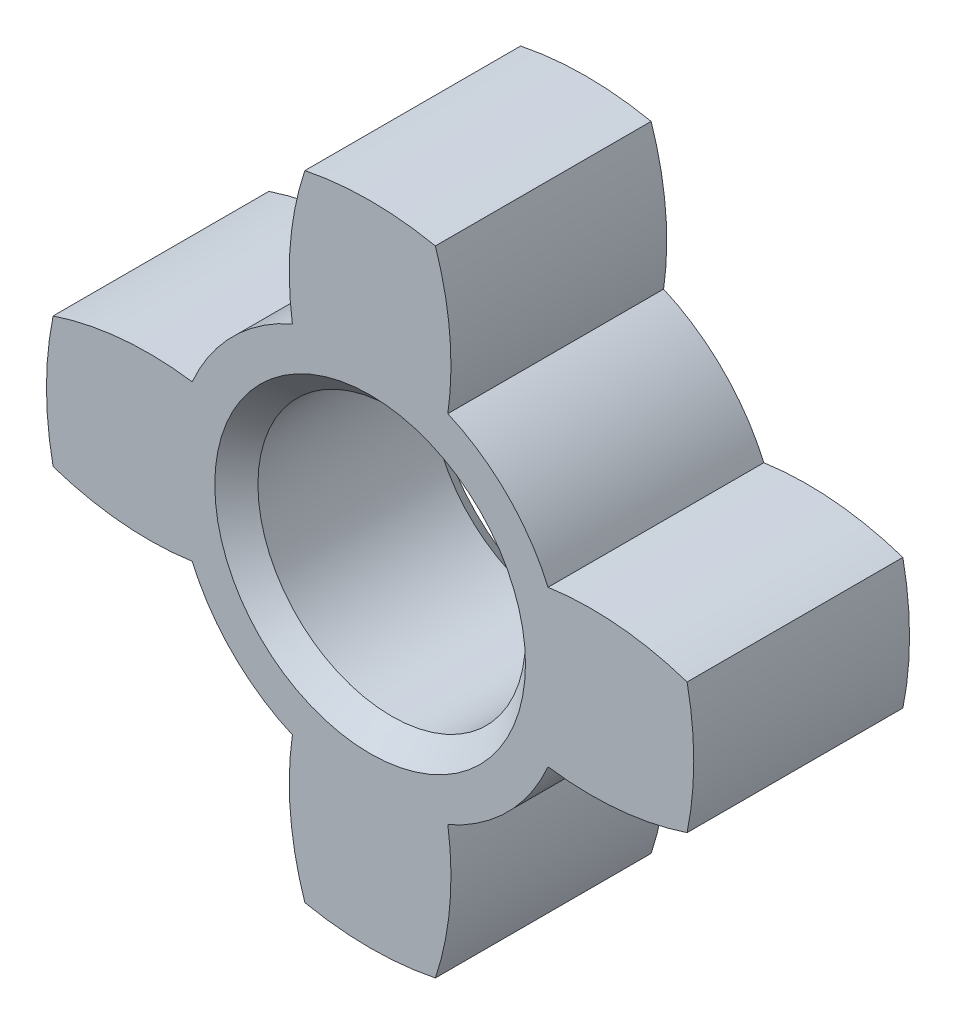
SolidWorks part; units mm, degrees
ref_plane "Front Plane" through (0, 0, 0) normal (0, 0, 1) x (1, 0, 0)
ref_plane "Top Plane" through (0, 0, 0) normal (0, 1, 0) x (1, 0, 0)
ref_plane "Right Plane" through (0, 0, 0) normal (1, 0, 0) x (0, 0, -1)
sketch "Sketch1" plane through (0, 0, 0) normal (1, 0, 0) x (0, 0, -1)
  line L0 (-5, 7.5) -> (-5, 3.6)
  line L1 (-5, 3.6) -> (-4.5, 3.1)
  line L2 (-4.5, 3.1) -> (-0.5, 3.1)
  line L3 (-0.5, 3.1) -> (0, 3.6)
  line L4 (0, 3.6) -> (0, 7.5)
  line L5 (0, 7.5) -> (-5, 7.5)
  line L6 (0, 0) -> (-5, 0) construction
revolve "Revolve1" add sketch "Sketch1" angle 360 about L6 reverse direction yes
sketch "Sketch2" plane through (0, 0, 0) normal (0, 0, 1) x (1, 0, 0)
  circle A0 centre (0, 0) radius 15
  arc A1 (-9.8929, 0) -> (-4.1238, -1.8013) centre (-5.1265, 5.1265) ccw
  arc A2 (-4.1238, -1.8013) -> (-1.8013, -4.1238) centre (0, 0) ccw
  arc A3 (-1.8013, -4.1238) -> (0, -9.8929) centre (5.1265, -5.1265) ccw
  arc A4 (0, -9.8929) -> (1.8013, -4.1238) centre (-5.1265, -5.1265) ccw
  arc A5 (1.8013, -4.1238) -> (4.1238, -1.8013) centre (0, 0) ccw
  arc A6 (4.1238, -1.8013) -> (9.8929, 0) centre (5.1265, 5.1265) ccw
  arc A7 (9.8929, 0) -> (4.1238, 1.8013) centre (5.1265, -5.1265) ccw
  arc A8 (4.1238, 1.8013) -> (1.8013, 4.1238) centre (0, 0) ccw
  arc A9 (1.8013, 4.1238) -> (0, 9.8929) centre (-5.1265, 5.1265) ccw
  arc A10 (0, 9.8929) -> (-1.8013, 4.1238) centre (5.1265, 5.1265) ccw
  arc A11 (-1.8013, 4.1238) -> (-4.1238, 1.8013) centre (0, 0) ccw
  arc A12 (-4.1238, 1.8013) -> (-9.8929, 0) centre (-5.1265, -5.1265) ccw
extrude "Cut-Extrude1" cut sketch "Sketch2" along normal blind 5
ref_plane "ANBAU XY" through (0, 0, 0) normal (0, 0, 1) x (1, 0, 0)
ref_plane "ANBAU XZ" through (0, 0, 0) normal (0, -1, 0) x (-1, 0, 0)
ref_plane "ANBAU YZ" through (0, 0, 0) normal (1, 0, 0) x (0, 0, -1)
ref_axis "ANBAU X" through (-80.9, 0, 0) along (1, 0, 0)
ref_axis "ANBAU Y" through (0, -50, 0) along (0, 1, 0)
ref_axis "ANBAU Z" through (0, 0, 80.9) along (0, 0, -1)
sketch3d "ANBAU"
  point P0 (0, 0, 0)
other "Freeze***"
